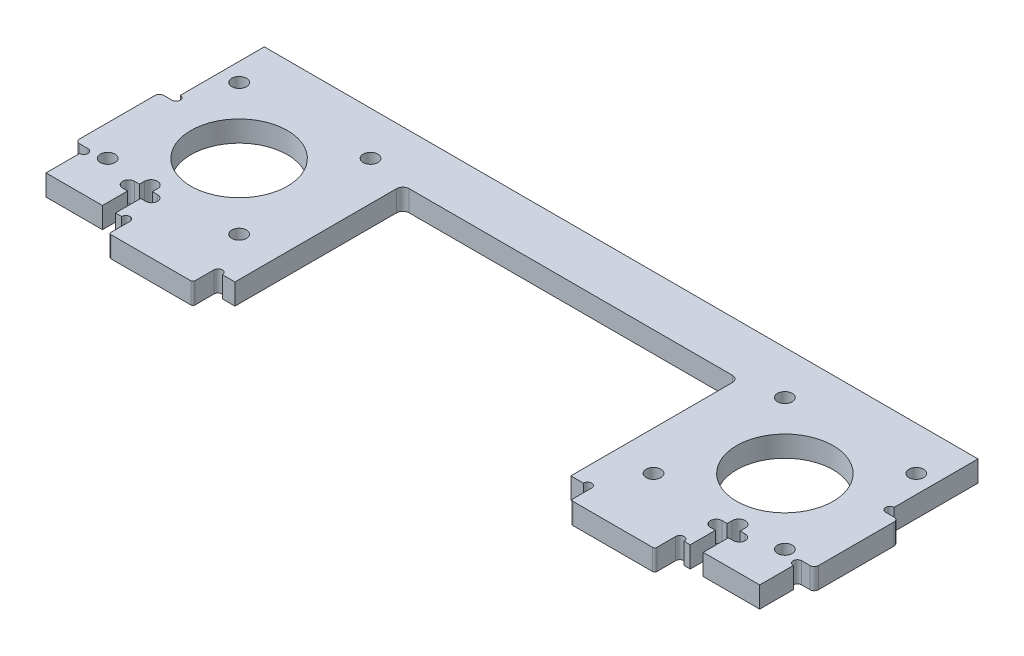
SolidWorks part; units mm, degrees
ref_plane "정면" through (0, 0, 0) normal (0, 0, 1) x (1, 0, 0)
ref_plane "윗면" through (0, 0, 0) normal (0, 1, 0) x (1, 0, 0)
ref_plane "우측면" through (0, 0, 0) normal (1, 0, 0) x (0, 0, -1)
sketch "스케치1" plane through (0, 0, 0) normal (0, 1, 0) x (1, 0, 0)
  line L1 (0, 0) -> (170, 0)
  line L2 (0, 0) -> (0, 52)
  line L3 (0, 52) -> (170, 52)
  line L4 (170, 0) -> (170, 52)
  dimension "D1" = 170
  dimension "D2" = 52
extrude "보스-돌출1" add sketch "스케치1" along normal blind 5
sketch "스케치2" plane through (0, 5, 0) normal (0, 1, 0) x (1, 0, 0)
  line L0 (85, 52) -> (85, 0) construction
  line L1 (170, 52) -> (0, 52) construction
  line L2 (0, 0) -> (170, 0) construction
  line L3 (150, 26) -> (20, 26) construction
  line L4 (134.35, 10.35) -> (165.65, 10.35) construction
  line L5 (134.35, 10.35) -> (134.35, 41.65) construction
  line L6 (134.35, 41.65) -> (165.65, 41.65) construction
  line L7 (165.65, 10.35) -> (165.65, 41.65) construction
  line L8 (134.35, 10.35) -> (165.65, 41.65) construction
  line L9 (134.35, 41.65) -> (165.65, 10.35) construction
  line L10 (170, 0) -> (170, 52) construction
  line L11 (35.65, 41.65) -> (4.35, 10.35) construction
  line L12 (35.65, 10.35) -> (4.35, 41.65) construction
  line L13 (4.35, 10.35) -> (4.35, 41.65) construction
  line L14 (35.65, 41.65) -> (4.35, 41.65) construction
  line L15 (35.65, 10.35) -> (35.65, 41.65) construction
  line L16 (35.65, 10.35) -> (4.35, 10.35) construction
  circle A0 centre (150, 26) radius 11.5
  circle A1 centre (165.65, 41.65) radius 1.75
  circle A2 centre (134.35, 41.65) radius 1.75
  circle A3 centre (165.65, 10.35) radius 1.75
  circle A4 centre (134.35, 10.35) radius 1.75
  circle A5 centre (35.65, 10.35) radius 1.75
  circle A6 centre (4.35, 10.35) radius 1.75
  circle A7 centre (35.65, 41.65) radius 1.75
  circle A8 centre (4.35, 41.65) radius 1.75
  circle A9 centre (20, 26) radius 11.5
  point P16 (170, 26)
  point P25 (85, 26)
  dimension "D1" = 23
  dimension "D3" = 3.5
  dimension "D2" = 31.3
  dimension "D4" = 20
extrude "컷-돌출1" cut sketch "스케치2" against normal blind 5
sketch "스케치3" plane through (0, 5, 0) normal (0, 1, 0) x (1, 0, 0)
  line L1 (0, 0) -> (170, 0) construction
  line L2 (130, 0) -> (150, 0)
  line L3 (130, 0) -> (130, -5)
  line L4 (130, -5) -> (150, -5)
  line L5 (150, 0) -> (150, -5)
  line L6 (130, -5) -> (40, -5) construction
  line L7 (20, 0) -> (40, 0)
  line L8 (20, 0) -> (20, -5)
  line L9 (20, -5) -> (40, -5)
  line L10 (40, 0) -> (40, -5)
  line L11 (150, -5) -> (170, -5) construction
  line L12 (170, -5) -> (170, 0) construction
  line L13 (0, 0) -> (0, -5) construction
  line L14 (0, -5) -> (20, -5) construction
  dimension "D1" = 20
  dimension "D2" = 20
  dimension "D3" = 5
extrude "보스-돌출2" add sketch "스케치3" against normal blind 5
sketch "스케치4" plane through (0, 5, 0) normal (0, 1, 0) x (1, 0, 0)
  line L0 (40, 0) -> (130, 0) construction
  line L1 (150, 0) -> (170, 0) construction
  line L2 (0, 0) -> (20, 0) construction
  circle A0 centre (129, 0) radius 1
  circle A1 centre (151, 0) radius 1
  circle A2 centre (19, 0) radius 1
  circle A3 centre (41, 0) radius 1
  dimension "D1" = 2
extrude "컷-돌출2" cut sketch "스케치4" against normal blind 5
sketch "스케치5" plane through (0, 5, 0) normal (0, 1, 0) x (1, 0, 0)
  line L0 (156.55, 0) -> (156.55, 6)
  line L1 (153.45, 10) -> (156.55, 10) construction
  line L2 (152.25, 6) -> (152.25, 8.8) construction
  line L3 (156.55, 6) -> (156.55, 8.8) construction
  line L4 (153.45, 0) -> (156.55, 0)
  line L5 (152.25, 8.8) -> (153.45, 8.8)
  line L6 (153.45, 0) -> (153.45, 6)
  line L7 (157.75, 8.8) -> (157.75, 6) construction
  line L8 (153.45, 6) -> (152.25, 6)
  line L9 (153.45, 8.8) -> (153.45, 6) construction
  line L10 (156.55, 8.8) -> (156.55, 10)
  line L11 (153.45, 6) -> (156.55, 6) construction
  line L12 (153.45, 8.8) -> (156.55, 8.8) construction
  line L13 (156.55, 8.8) -> (157.75, 8.8)
  line L14 (153.45, 8.8) -> (153.45, 10)
  line L15 (155, 10) -> (155, 12.1831) construction
  line L16 (157.75, 6) -> (156.55, 6)
  line L34 (170, 0) -> (170, 52) construction
  line L35 (85, 52) -> (85, 0) construction
  line L36 (170, 52) -> (0, 52) construction
  line L37 (42, 0) -> (128, 0) construction
  line L46 (15, 10) -> (15, 12.1831) construction
  line L47 (16.55, 8.8) -> (13.45, 8.8) construction
  line L48 (16.55, 6) -> (13.45, 6) construction
  line L49 (16.55, 8.8) -> (16.55, 6) construction
  line L50 (12.25, 8.8) -> (12.25, 6) construction
  line L51 (13.45, 6) -> (13.45, 8.8) construction
  line L52 (17.75, 6) -> (17.75, 8.8) construction
  line L53 (16.55, 10) -> (13.45, 10) construction
  line L63 (12.25, 6) -> (13.45, 6)
  line L64 (16.55, 8.8) -> (16.55, 10)
  line L65 (13.45, 8.8) -> (12.25, 8.8)
  line L66 (13.45, 8.8) -> (13.45, 10)
  line L67 (16.55, 6) -> (17.75, 6)
  line L68 (16.55, 0) -> (16.55, 6)
  line L69 (17.75, 8.8) -> (16.55, 8.8)
  line L70 (16.55, 0) -> (13.45, 0)
  line L71 (13.45, 0) -> (13.45, 6)
  arc A0 (156.55, 10) -> (153.45, 10) centre (155, 10) ccw
  arc A1 (152.25, 8.8) -> (152.25, 6) centre (152.25, 7.4) ccw
  arc A2 (157.75, 6) -> (157.75, 8.8) centre (157.75, 7.4) ccw
  arc A9 (12.25, 6) -> (12.25, 8.8) centre (12.25, 7.4) cw
  arc A10 (17.75, 8.8) -> (17.75, 6) centre (17.75, 7.4) cw
  arc A11 (13.45, 10) -> (16.55, 10) centre (15, 10) cw
  dimension "D1" = 3.1
  dimension "D2" = 10
  dimension "D3" = 5.5
  dimension "D4" = 2.8
  dimension "D12" = 15
extrude "컷-돌출3" cut sketch "스케치5" against normal blind 10
fillet "필렛1" radius 0.5 4 edges at (20, 2.5, 5) (130, 2.5, 5) (150, 2.5, 5) (40, 2.5, 5)
sketch "스케치6" plane through (0, 5, 0) normal (0, 1, 0) x (1, 0, 0)
  line L0 (85, 52) -> (85, 0) construction
  line L1 (170, 52) -> (0, 52) construction
  line L3 (85, 21) -> (85, 31) construction
  line L4 (81, 21) -> (81, 31)
  line L5 (89, 21) -> (89, 31)
  arc A0 (81, 21) -> (89, 21) centre (85, 21) ccw
  arc A1 (89, 31) -> (81, 31) centre (85, 31) ccw
  point P8 (85, 26)
  dimension "D1" = 4
  dimension "D2" = 10
extrude "컷-돌출4" [suppressed] cut sketch "스케치6" against normal blind 10
sketch "스케치7" plane through (0, 5, 0) normal (0, 1, 0) x (1, 0, 0)
  line L0 (170, 0) -> (170, 52) construction
  line L1 (170, 30) -> (173, 30)
  line L2 (170, 30) -> (170, 10)
  line L3 (170, 10) -> (173, 10)
  line L4 (173, 30) -> (173, 10)
  line L5 (0, 52) -> (0, 0) construction
  line L6 (0, 30) -> (-3, 30)
  line L7 (0, 30) -> (0, 10)
  line L8 (0, 10) -> (-3, 10)
  line L9 (-3, 30) -> (-3, 10)
  line L10 (156.55, 0) -> (170, 0) construction
  dimension "D1" = 3
  dimension "D2" = 10
  dimension "D3" = 20
extrude "보스-돌출3" add sketch "스케치7" against normal blind 5
sketch "스케치8" plane through (0, 5, 0) normal (0, 1, 0) x (1, 0, 0)
  line L0 (170, 0) -> (170, 10) construction
  line L1 (170, 30) -> (170, 52) construction
  line L2 (0, 10) -> (0, 0) construction
  line L3 (0, 52) -> (0, 30) construction
  circle A0 centre (170, 9) radius 1
  circle A1 centre (170, 31) radius 1
  circle A2 centre (0, 9) radius 1
  circle A3 centre (0, 31) radius 1
  dimension "D1" = 2
extrude "컷-돌출5" cut sketch "스케치8" against normal blind 5
sketch "스케치9" plane through (0, 5, 0) normal (0, 1, 0) x (1, 0, 0)
  line L0 (85, 52) -> (85, 0) construction
  line L1 (170, 52) -> (0, 52) construction
  line L2 (42, 0) -> (128, 0) construction
  line L4 (45, 40) -> (125, 40)
  line L5 (45, 40) -> (45, 0)
  line L6 (45, 0) -> (125, 0)
  line L7 (125, 40) -> (125, 0)
  line L8 (45, 40) -> (125, 0) construction
  line L9 (45, 0) -> (125, 40) construction
  point P6 (85, 20)
  dimension "D1" = 40
  dimension "D2" = 80
extrude "컷-돌출6" cut sketch "스케치9" against normal blind 10
fillet "필렛2" radius 1.5 2 edges at (125, 2.5, -40) (45, 2.5, -40)
fillet "필렛3" radius 1 4 edges at (173, 2.5, -10) (173, 2.5, -30) (-3, 2.5, -10) (-3, 2.5, -30)
